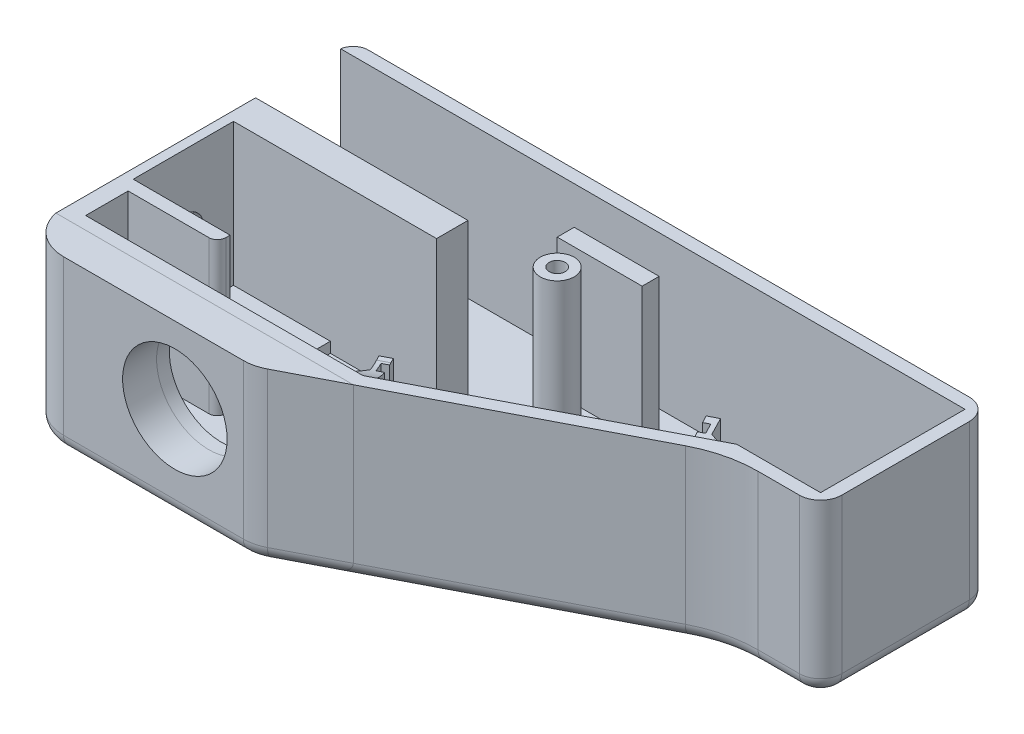
SolidWorks part; units mm, degrees
ref_plane "Front Plane" through (0, 0, 0) normal (0, 0, 1) x (1, 0, 0)
ref_plane "Top Plane" through (0, 0, 0) normal (0, 1, 0) x (1, 0, 0)
ref_plane "Right Plane" through (0, 0, 0) normal (1, 0, 0) x (0, 0, -1)
sketch "Sketch1" plane through (0, 0, 0) normal (0, 1, 0) x (1, 0, 0)
  line L5 (0, 0) -> (95.25, 0)
  line L6 (95.25, 0) -> (95.25, -25.4)
  line L7 (95.25, -25.4) -> (81.28, -25.4)
  line L8 (81.28, -25.4) -> (44.45, -44.45)
  line L9 (44.45, -44.45) -> (0, -44.45)
  line L10 (0, -44.45) -> (0, 0)
  dimension "D1" = 44.45
  dimension "D2" = 44.45
  dimension "D3" = 95.25
  dimension "D4" = 25.4
  dimension "D5" = 13.97
extrude "Boss-Extrude1" add sketch "Sketch1" along normal blind 2.54
sketch "Sketch2" plane through (0, 2.54, 0) normal (0, 1, 0) x (1, 0, 0)
  line L0 (0, 0) -> (0, -1.905)
  line L1 (0, 0) -> (0, -44.45) construction
  line L2 (0, -1.905) -> (93.345, -1.905)
  line L3 (93.345, -1.905) -> (93.345, -23.495)
  line L4 (93.345, -23.495) -> (80.8165, -23.495)
  line L5 (80.8165, -23.495) -> (43.9865, -42.545)
  line L6 (43.9865, -42.545) -> (0, -42.545)
  line L7 (0, -42.545) -> (0, -44.45)
  line L8 (0, -44.45) -> (44.45, -44.45)
  line L9 (44.45, -44.45) -> (81.28, -25.4)
  line L10 (81.28, -25.4) -> (95.25, -25.4)
  line L11 (95.25, -25.4) -> (95.25, 0)
  line L12 (95.25, 0) -> (0, 0)
  dimension "D1" = 1.905
  dimension "D2" = 1.905
  dimension "D3" = 1.905
  dimension "D4" = 1.905
  dimension "D5" = 1.905
extrude "Boss-Extrude2" add sketch "Sketch2" along normal blind 22.7965
sketch "Sketch3" plane through (0, 2.54, 0) normal (0, 1, 0) x (1, 0, 0)
  line L0 (0, -1.905) -> (0, -42.545) construction
  line L1 (0, -19.304) -> (31.75, -19.304)
  line L2 (0, -19.304) -> (0, -14.605)
  line L3 (0, -14.605) -> (31.75, -14.605)
  line L4 (31.75, -19.304) -> (31.75, -14.605)
  line L5 (0, -1.905) -> (93.345, -1.905) construction
  line L8 (0, -34.29) -> (15.875, -34.29)
  line L9 (0, -34.29) -> (0, -36.195)
  line L10 (0, -36.195) -> (15.875, -36.195)
  line L11 (15.875, -34.29) -> (15.875, -36.195)
  dimension "D1" = 19.304
  dimension "D2" = 12.7
  dimension "D3" = 31.75
  dimension "D4" = 14.986
  dimension "D5" = 1.905
  dimension "D6" = 15.875
extrude "Boss-Extrude3" add sketch "Sketch3" along normal blind 22.7965
sketch "Sketch4" plane through (0, 0, 0) normal (-1, 0, 0) x (0, 0, 1)
  line L0 (39.37, 25.3365) -> (39.37, 2.54) construction
  line L1 (36.195, 25.3365) -> (42.545, 25.3365)
  line L2 (36.195, 25.3365) -> (36.195, 2.54)
  line L3 (36.195, 2.54) -> (42.545, 2.54)
  line L4 (42.545, 25.3365) -> (42.545, 2.54)
  line L5 (36.195, 13.9383) -> (42.545, 13.9383) construction
  line L7 (40.1955, 16.3513) -> (38.5445, 16.3513)
  line L8 (40.1955, 16.3513) -> (40.1955, 11.5253)
  line L9 (40.1955, 11.5253) -> (38.5445, 11.5253)
  line L10 (38.5445, 16.3513) -> (38.5445, 11.5253)
  line L11 (40.1955, 16.3513) -> (38.5445, 11.5253) construction
  line L12 (40.1955, 11.5253) -> (38.5445, 16.3513) construction
  point P10 (39.37, 13.9383)
  dimension "D1" = 1.651
  dimension "D2" = 4.826
  dimension "D3" = 11.3983
extrude "Boss-Extrude4" add sketch "Sketch4" against normal blind 2.54
fillet "Fillet5" radius 1.27 1 edges at (15.875, 13.9383, 36.195)
sketch "Sketch6" plane through (0, 25.3365, 0) normal (0, 1, 0) x (1, 0, 0)
  line L1 (0, -44.45) -> (44.45, -44.45)
  line L2 (0, -44.45) -> (0, -49.53)
  line L3 (0, -49.53) -> (44.45, -49.53)
  line L4 (44.45, -44.45) -> (44.45, -49.53)
  dimension "D1" = 5.08
extrude "Boss-Extrude5" add sketch "Sketch6" against normal up to surface (25.3365 mm away) separate body up to face at (52.705, 0, 23.2833)
sketch "Sketch7" plane through (0, 0, 49.53) normal (0, 0, 1) x (1, 0, 0)
  line L0 (38.1, 13.9383) -> (0, 13.9382) construction
  line L3 (44.45, 25.3365) -> (44.45, 0) construction
  line L4 (0, 0) -> (44.45, 0) construction
  circle A0 centre (22.86, 13.9383) radius 7.8105
  dimension "D1" = 15.621
  dimension "D2" = 21.59
  dimension "D3" = 13.9383
extrude "Cut-Extrude1" cut sketch "Sketch7" against normal up to surface (6.985 mm away) up to face at (23.2632, 13.9383, 42.545)
sketch "Sketch9" plane through (0, 25.3365, 0) normal (0, 1, 0) x (1, 0, 0)
  line L0 (44.45, -44.45) -> (34.6287, -49.53)
  line L1 (0, -49.53) -> (44.45, -49.53) construction
  line L2 (34.6287, -49.53) -> (44.45, -49.53)
  line L3 (44.45, -49.53) -> (44.45, -44.45)
  line L4 (44.45, -44.45) -> (81.28, -25.4) construction
extrude "Cut-Extrude2" cut sketch "Sketch9" against normal through all
sketch "Sketch10" plane through (0, 2.54, 0) normal (0, 1, 0) x (1, 0, 0)
  line L0 (95.25, -25.4) -> (95.25, 0) construction
  line L1 (81.28, -25.4) -> (95.25, -25.4) construction
  circle A0 centre (44.45, -13.97) radius 2.54
  circle A2 centre (44.45, -13.97) radius 1.2065
  dimension "D1" = 5.08
  dimension "D2" = 2.413
  dimension "D3" = 50.8
  dimension "D4" = 11.43
extrude "Boss-Extrude6" add sketch "Sketch10" along normal up to surface (22.7965 mm away) up to face at (39.9659, 25.3365, 26.5734)
fillet "Fillet6" radius 19.05 1 edges at (81.28, 12.6682, 25.4)
fillet "Fillet7" radius 6.35 2 edges at (0, 12.6682, 49.53) (34.6287, 12.6682, 49.53)
fillet "Fillet8" radius 3.175 2 edges at (95.25, 12.6682, 25.4) (95.25, 12.6682, 0)
fillet "Fillet9" radius 2.2225 7 edges at (46.0375, 0, 0) (94.3201, 0, 0.9299) (95.25, 0, 12.7) (94.3201, 0, 24.4701) (88.995, 0, 25.4) (60.8065, 0, 35.9897) (81.4114, 0, 25.94)
fillet "Fillet10" radius 2.2225 4 edges at (2.2056, 0, 48.0987) (40.2255, 0, 46.6351) (34.5849, 0, 49.35) (19.6527, 0, 49.53)
fillet "Fillet11" radius 2.2225 3 edges at (0, 13.7795, 0) (0, 0.651, 0.651) (0, 0, 23.3362)
sketch "Sketch11" plane through (0, 2.54, 0) normal (0, 1, 0) x (1, 0, 0)
  line L1 (0, -19.304) -> (15.875, -19.304)
  line L2 (0, -19.304) -> (0, -34.29)
  line L3 (0, -34.29) -> (15.875, -34.29)
  line L4 (15.875, -19.304) -> (15.875, -34.29)
extrude "Boss-Extrude7" add sketch "Sketch11" along normal blind 1.5684
sketch "Sketch12" plane through (0, 0, 0) normal (-1, 0, 0) x (0, 0, 1)
  line L0 (26.797, 25.3365) -> (26.797, 4.1084) construction
  line L1 (19.304, 25.3365) -> (34.29, 25.3365)
  line L2 (19.304, 25.3365) -> (19.304, 4.1084)
  line L3 (19.304, 4.1084) -> (34.29, 4.1084)
  line L4 (34.29, 25.3365) -> (34.29, 4.1084)
  line L5 (19.304, 13.9763) -> (34.29, 13.9764) construction
  circle A0 centre (26.797, 13.9763) radius 3.048
  dimension "D1" = 6.096
  dimension "D2" = 9.8679
extrude "Boss-Extrude8" add sketch "Sketch12" against normal blind 1.397
sketch "Sketch14" plane through (0, 0, 0) normal (0, 0, -1) x (-1, 0, 0)
  line L0 (-95.25, 13.7795) -> (-0.0228, 13.9383) construction
  line L3 (-95.25, 2.2225) -> (-95.25, 25.3365) construction
  line L5 (-0.0228, 25.3365) -> (-0.0228, 2.54) construction
  circle A0 centre (-86.868, 13.7935) radius 2.5781
  dimension "D1" = 5.1562
  dimension "D2" = 8.382
extrude "Cut-Extrude3" cut sketch "Sketch14" against normal up to surface (1.905 mm away) up to face at (46.6839, 13.9383, 1.905)
sketch "Sketch15" plane through (0, 2.54, 0) normal (0, 1, 0) x (1, 0, 0)
  line L0 (31.75, -19.304) -> (31.75, -14.605) construction
  line L1 (38.1, -5.08) -> (50.8, -5.08)
  line L2 (38.1, -5.08) -> (38.1, -7.62)
  line L3 (38.1, -7.62) -> (50.8, -7.62)
  line L4 (50.8, -5.08) -> (50.8, -7.62)
  line L5 (0.0228, -1.905) -> (93.345, -1.905) construction
  point P4 (38.1, -6.35)
  dimension "D1" = 12.7
  dimension "D2" = 2.54
  dimension "D3" = 6.35
  dimension "D4" = 3.175
extrude "Boss-Extrude9" add sketch "Sketch15" along normal blind 20.32
sketch "Sketch16" plane through (0, 4.1084, 0) normal (0, 1, 0) x (1, 0, 0)
  line L0 (15.875, -19.304) -> (1.397, -19.304) construction
  line L1 (10.795, -24.384) -> (20.447, -24.384)
  line L2 (10.795, -24.384) -> (10.795, -29.337)
  line L3 (10.795, -29.337) -> (20.447, -29.337)
  line L4 (20.447, -24.384) -> (20.447, -29.337)
  line L5 (15.875, -34.29) -> (15.875, -19.304) construction
  dimension "D1" = 5.08
  dimension "D2" = 4.953
  dimension "D3" = 9.652
  dimension "D4" = 5.08
extrude "Cut-Extrude4" cut sketch "Sketch16" against normal blind 3.302
sketch "Sketch17" plane through (0, 2.54, 0) normal (0, 1, 0) x (1, 0, 0)
  line L0 (43.9865, -42.545) -> (41.4192, -37.5816)
  line L1 (41.4192, -37.5816) -> (42.8293, -36.8523)
  line L2 (42.8293, -36.8523) -> (43.4128, -37.9803)
  line L3 (43.4128, -37.9803) -> (42.5667, -38.4179)
  line L5 (80.8165, -23.495) -> (43.9865, -42.545) construction
  line L6 (45.3965, -41.8157) -> (43.9865, -42.545)
  line L8 (42.5667, -38.4179) -> (43.3836, -39.9972)
  line L9 (43.3836, -39.9972) -> (44.2296, -39.5596)
  line L10 (44.2296, -39.5596) -> (45.3965, -41.8157)
  line L11 (76.2258, -25.8695) -> (75.0588, -23.6134)
  line L12 (75.0588, -23.6134) -> (75.871, -23.1933)
  line L13 (75.871, -23.1933) -> (75.0542, -21.6141)
  line L14 (75.0542, -21.6141) -> (74.242, -22.0342)
  line L15 (74.242, -22.0342) -> (73.6585, -20.9061)
  line L16 (73.6585, -20.9061) -> (75.0686, -20.1768)
  line L17 (75.0686, -20.1768) -> (77.6358, -25.1402)
  line L18 (80.8165, -23.495) -> (43.9865, -42.545) construction
  line L19 (77.6358, -25.1402) -> (76.2258, -25.8695)
  dimension "D1" = 1.778
  dimension "D2" = 0.9144
  dimension "D3" = 4.318
  dimension "D4" = 1.27
  dimension "D5" = 1.5875
  dimension "D6" = 0.9525
  dimension "D7" = 36.576
extrude "Boss-Extrude10" add sketch "Sketch17" along normal blind 21.59
chamfer "Chamfer1" distance 2.54 angle 45 2 edges at (43.9865, 13.335, 42.545) (77.6358, 13.335, 25.1402) first distance on face at (42.7029, 13.335, 40.0633) first distance on face at (64.8122, 15.7353, 31.7731)
fillet "Fillet12" radius 10 1 edges at (44.6915, 24.13, 42.1803)
fillet "Fillet13" radius 2.54 1 edges at (44.45, 2.54, 11.43)
sketch "Sketch19" plane through (0, 0, 0) normal (-1, 0, 0) x (0, 0, 1)
  line L0 (38.5445, 11.5253) -> (40.1955, 11.5253) construction
  line L1 (38.5445, 16.3513) -> (35.2425, 16.3513)
  line L2 (38.5445, 16.3513) -> (38.5445, 11.5253)
  line L3 (38.5445, 11.5253) -> (35.2425, 11.5253)
  line L4 (35.2425, 16.3513) -> (35.2425, 11.5253)
  dimension "D1" = 3.302
extrude "Cut-Extrude5" cut sketch "Sketch19" against normal blind 1.905
chamfer "Chamfer2" distance 0.635 angle 63 1 edges at (1.905, 13.9383, 38.5445) first distance on face at (2.2225, 13.9383, 38.5445)
